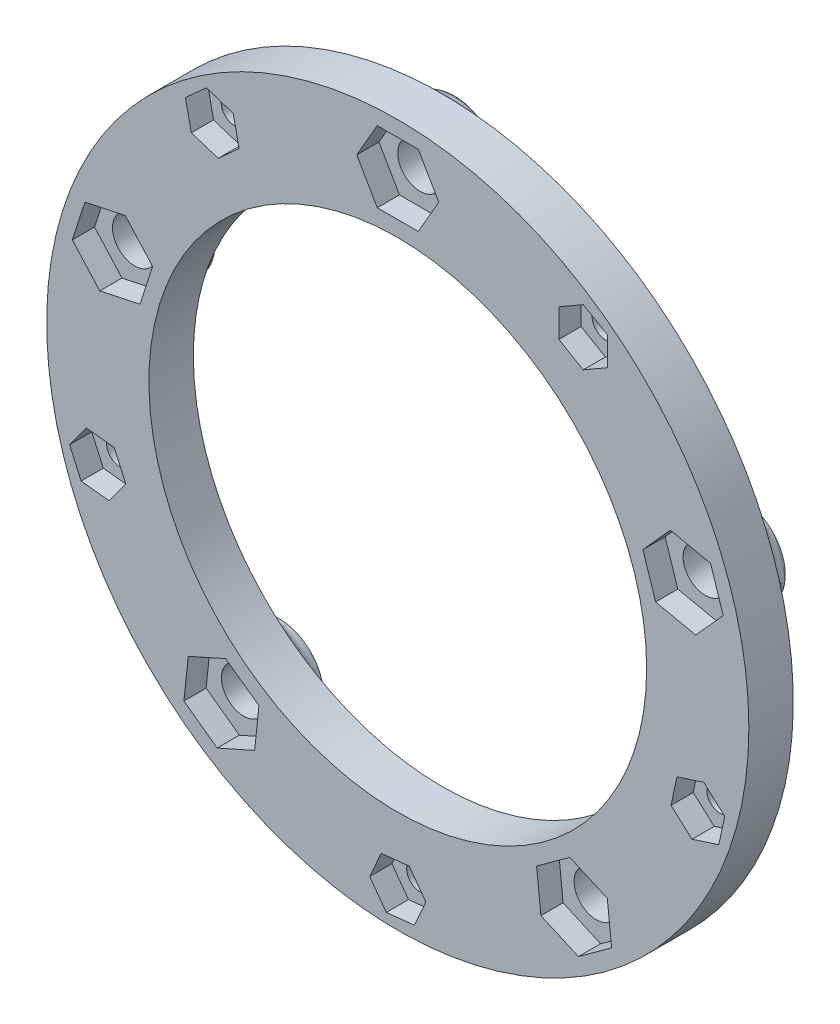
SolidWorks part; units mm, degrees
material "PLA"
ref_plane "Front Plane" through (0, 0, 0) normal (0, 0, 1) x (1, 0, 0)
ref_plane "Top Plane" through (0, 0, 0) normal (0, 1, 0) x (1, 0, 0)
ref_plane "Right Plane" through (0, 0, 0) normal (1, 0, 0) x (0, 0, -1)
sketch "Sketch2" plane through (0, 0, 0) normal (0, 0, 1) x (1, 0, 0)
  line L0 (0, 33.75) -> (0, 0) construction
  line L1 (0, 0) -> (20.8664, 28.7201) construction
  circle A0 centre (0, 0) radius 39.5
  circle A2 centre (0, 0) radius 33.75 construction
  circle A3 centre (0, 33.75) radius 2.5
  circle A4 centre (0, 0) radius 35.5 construction
  circle A5 centre (32.0982, 10.4293) radius 2.5
  circle A8 centre (20.8664, 28.7201) radius 1.5
  circle A9 centre (33.7625, -10.9701) radius 1.5
  circle A11 centre (0, 0) radius 20 construction
  circle A14 centre (0, 33.75) radius 4.25 construction
  circle A15 centre (0, 0) radius 29.5 construction
  circle A16 centre (19.8378, -27.3043) radius 2.5
  circle A19 centre (0, -35.5) radius 1.5
  circle A20 centre (0, 0) radius 38 construction
  circle A23 centre (0, 0) radius 28
  circle A36 centre (-19.8378, -27.3043) radius 2.5
  circle A37 centre (-32.0982, 10.4293) radius 2.5
  circle A38 centre (-33.7625, -10.9701) radius 1.5
  circle A39 centre (-20.8664, 28.7201) radius 1.5
  point P17 (0, 0)
  point P24 (0, 0)
  dimension "D2" = 67.5
  dimension "D4" = 5
  dimension "D7" = 3
  dimension "D3" = 40
  dimension "D10" = 8.5
  dimension "D5" = 4
  dimension "D11" = 36
  dimension "D12" = 1.5
  dimension "D9" = 1.5
  dimension "D6" = 5
  dimension "D8" = 5
extrude "Boss-Extrude1" add sketch "Sketch2" along normal blind 5
sketch "Sketch3" plane through (0, 0, 5) normal (0, 0, 1) x (1, 0, 0)
  line L0 (0, 33.75) -> (0, 0) construction
  line L13 (-4.6188, 33.75) -> (-2.3094, 29.75)
  line L14 (-2.3094, 29.75) -> (2.3094, 29.75)
  line L15 (2.3094, 29.75) -> (4.6188, 33.75)
  line L16 (4.6188, 33.75) -> (2.3094, 37.75)
  line L17 (2.3094, 37.75) -> (-2.3094, 37.75)
  line L18 (-2.3094, 37.75) -> (-4.6188, 33.75)
  line L20 (20.8664, 25.5447) -> (23.6164, 27.1324)
  line L21 (23.6164, 27.1324) -> (23.6164, 30.3078)
  line L22 (23.6164, 30.3078) -> (20.8664, 31.8955)
  line L23 (20.8664, 31.8955) -> (18.1164, 30.3078)
  line L24 (18.1164, 30.3078) -> (18.1164, 27.1324)
  line L25 (18.1164, 27.1324) -> (20.8664, 25.5447)
  circle A0 centre (0, 33.75) radius 4 construction
  circle A1 centre (20.8664, 28.7201) radius 2.75 construction
  dimension "D1" = 8
  dimension "D2" = 5.5
extrude "Cut-Extrude1" cut sketch "Sketch3" against normal blind 2.5
pattern_circular "CirPattern1" count 5 over 360 about axis through (0, 0, 5) along (0, 0, -1) of "Cut-Extrude1" reverse direction yes
sketch "Sketch4" plane through (0, 0, 0) normal (0, 0, -1) x (-1, 0, 0)
  circle A0 centre (0, 33.75) radius 4
  circle A1 centre (0, 33.75) radius 5
  dimension "D1" = 8
extrude "Boss-Extrude2" add sketch "Sketch4" along normal blind 1.5
fillet "Fillet1" radius 1.5 1 edges at (5, 33.75, 0)
fillet "Fillet2" radius 0.5 4 edges at (0, 38.75, -1.5) (0, 28.75, -1.5) (4.9949, 33.5246, -1.5) (-4.9949, 33.5246, -1.5)
chamfer "Chamfer1" distance 0.25 angle 45 1 edges at (-4, 33.75, -1.5)
pattern_circular "CirPattern2" count 5 over 360 about axis through (0, 0, 5) along (0, 0, -1) of "Fillet1", "Boss-Extrude2", "Chamfer1" reverse direction yes
equation "\"module\" = 0.5"
equation "\"pressure_angle\" = 20.0"
equation "\"h_a\" = 0.5"
equation "\"h_f\" = 0.625"
equation "\"clr_tip_root\" = 0.125"
equation "\"bearing_ID\" = 75"
equation "\"bearing_OD\" = 95"
equation "\"bearing_height\" = 10"
equation "\"clearance_planet\" = 1.5"
equation "\"case_dist\" = 6.5"
equation "\"Motor_case_OD_max\" = 131.3"
equation "\"case_mounting_PCD\" = 123.8"
equation "\"bearing mount thickness\" = 8"
equation "\"case_mounting_hole_dia\" = 3"
equation "\"output_mounting_PCD\" = 103"
equation "\"output_mounting_hole_dia\" = 4"
equation "\"clearance_case_mount_holes_shell_thickness\" = 1"
equation "\"motor_case_OD_base\" = 121.8"
equation "\"sec_carrier_thickness\" = 5"
equation "\"sun_coupler_hub_thickness\" = 4"
equation "\"clearance_sun_coupler_sec_carrier\" = 1.5"
equation "\"clearance_motor_and_case\" = 5"
equation "\"motor_OD\" = 106.8"
equation "\"Motor_case_thickness\" = 2.5"
equation "\"Motor_case_ID\" = 116.8"
equation "\"case_mounting_hole_shift\" = 1.0"
equation "\"output_mounting_nut_wrench_size\" = 7"
equation "\"output_mounting_nut_thickness\" = 3.2"
equation "\"case_mounting_hole_allen_socket_dia\" = 5.5"
equation "\"output_mounting_nut_depth\" = 3"
equation "\"case_mounting_bolt_depth\" = 4.5"
equation "\"Ns\" = 80"
equation "\"Np_b\" = 55"
equation "\"ring_radial_thickness\" = 5"
equation "\"ring_to_chamfer_clearance\" = 1.5"
equation "\"Motor_case_OD_base_to_chamfer\" = 5"
equation "\"pattern_offset_from_motor_case_OD_base\" = 3"
equation "\"pattern_bulge_dia\" = 3"
equation "\"pattern_num_bulge\" = 18"
equation "\"pattern_depth\" = 2"
equation "\"motor_height\" = 47.6"
equation "\"case_mounting_wrench_size\" = 5.5"
equation "\"case_mounting_nut_clearance\" = 2"
equation "\"base_plate_thickness\" = 4"
equation "\"case_mounting_nut_thickness\" = 2.4"
equation "\"case_mounting_surface_height\" = 4"
equation "\"motor_mount_hole_PCD\" = 40"
equation "\"motor_mount_hole_dia\" = 5"
equation "\"motor_mount_hole_num\" = 4"
equation "\"central_hole_offset_from_motor_mount_PCD\" = 5"
equation "\"wire_slot_dist_from_center\" = 45.5"
equation "\"wire_slot_length\" = 10"
equation "\"wire_slot_radius\" = 3"
equation "\"driver_upper_holes_dist_from_center\" = 29"
equation "\"driver_lower_holes_dist_from_center\" = 13"
equation "\"driver_side_holes_dist_from_center\" = 22.5"
equation "\"driver_mount_holes_dia\" = 3"
equation "\"driver_mount_inserts_OD\" = 4.8"
equation "\"driver_mount_thickness\" = 1.5"
equation "\"driver_mount_height\" = 6"
equation "\"air_flow_hole_offset\" = 3"
equation "\"num_planet\" = 5"
equation "\"planet_pin_bolt_dia\" = 5"
equation "\"planet_pin_socket_head_dia\" = 8.5"
equation "\"carrier_PCD\" = 67.5"
equation "\"D2@Sketch2\"=\"carrier_PCD\""
equation "\"D4@Sketch2\"=\"planet_pin_bolt_dia\""
equation "\"D6@Sketch2\"=\"num_planet\""
equation "\"D8@Sketch2\"=\"num_planet\""
equation "\"D1@CirPattern1\"=\"num_planet\""
equation "\"planet_shaft_dia\" = 8"
equation "\"planet_shaft_step_offset\" = 1"
equation "\"carrier_trapezoidal_support_sun_offset\" = 5"
equation "\"carrier_trapezoidal_support_hole_PCD_offset_bearing_ID\" = 4"
equation "\"carrier_trapezoidal_support_hole_dia\" = 3"
equation "\"carrier_trapezoidal_support_hole_socket_head_dia\" = 5.5"
equation "\"carrier_bearing_step_width\" = 1.5"
equation "\"standard_clearance_1_5mm\" = 1.5"
equation "\"standard_fillet_1_5mm\" = 1.5"
equation "\"sun_shaft_bearing_OD\" = 16"
equation "\"sun_shaft_bearing_width\" = 5"
equation "\"standard_bearing_insertion_chamfer\" = 0.5"
equation "\"D7@Sketch2\"=\"carrier_trapezoidal_support_hole_dia\""
equation "\"D3@Sketch2\"=\"Ns\"*\"module\""
equation "\"carrier_trapezoidal_support_hole_wrench_size\" = 5.5"
equation "\"planet_pin_bolt_wrench_size\" = 8"
equation "\"D1@Boss-Extrude1\"=\"sec_carrier_thickness\""
equation "\"D1@Cut-Extrude1\"=\"sec_carrier_thickness\"/2"
equation "\"D1@Sketch4\"=\"planet_shaft_dia\""
equation "\"D2@Sketch4\"=\"planet_shaft_step_offset\""
equation "\"D1@Boss-Extrude2\"=\"clearance_planet\""
equation "\"D1@Fillet1\"=\"standard_fillet_1_5mm\""
equation "\"D1@Chamfer1\"=\"standard_bearing_insertion_chamfer\"/2"
equation "\"D1@Fillet2\"=\"standard_fillet_1_5mm\"/3"
equation "\"D1@CirPattern2\"=\"num_planet\""
equation "\"D10@Sketch2\"= \"planet_pin_socket_head_dia\""
equation "\"D1@Sketch3\"=\"planet_pin_bolt_wrench_size\""
equation "\"D11@Sketch2\"=180/\"num_planet\""
equation "\"D2@Sketch3\"=\"carrier_trapezoidal_support_hole_wrench_size\""
equation "\"pressure angle\" = 20.0"
equation "\"h_b\" = 0.625"
equation "\"dp_s\" = 40.0"
equation "\"db_s\" = 37.58770483143634"
equation "\"fw_s_calc\" = 4.872946430626146"
equation "\"alpha_s\" = 0.8539582918412272"
equation "\"beta_s\" = 0.5420834163175456"
equation "\"dp_p_b\" = 27.5"
equation "\"db_p_b\" = 25.84154707161248"
equation "\"fw_p_s\" = 15.81085678360617"
equation "\"alpha_p_b\" = 0.8539582918412449"
equation "\"beta_p_b\" = 1.564810689044783"
equation "\"planet_bearing_OD\" = 12"
equation "\"planet_bearing_width\" = 3.5"
equation "\"planet_bore\" = 10"
equation "\"motor_output_hole_PCD\" = 23"
equation "\"motor_output_hole_dia\" = 4"
equation "\"motor_output_hole_num\" = 4"
equation "\"sun_shaft_bearing_ID\" = 8"
equation "\"sun_hub_dia\" = 30.0"
equation "\"sun_central_bolt_dia\" = 5"
equation "\"sun_central_bolt_socket_head_dia\" = 8.5"
equation "\"fw_s_used\" = 44.67596466627659"
equation "\"motor_output_hole_CSK_OD\" = 8"
equation "\"motor_output_hole_CSK_head_height\" = 2.0"
equation "\"bearing_retainer_thickness\" = 2"
equation "\"Np_s\" = 35"
equation "\"fw_p_b\" = 21.365107882670422"
equation "\"dp_p_s\" = 17.5"
equation "\"db_p_s\" = 16.444620863753396"
equation "\"alpha_p_s\" = 0.8539582918412556"
equation "\"beta_p_s\" = 3.434940559174632"
equation "\"Nr_b\" = 190"
equation "\"dp_r_b\" = 95.0"
equation "\"db_r_b\" = 89.2707989746613"
equation "\"fw_r_b\" = 21.365107882670422"
equation "\"alpha_r_b\" = 0.8539582918412414"
equation "\"beta_r_b\" = 2.655285004735114"
equation "\"ring_OD_b\" = 105.0"
equation "\"Fillet10\"= IIF ( \"ring_OD_b\" > ( \"bearing_OD\" + 2 * \"bearing mount thickness\" ) , \"suppressed\" , \"unsuppressed\" )"
equation "\"Fillet11\"= IIF ( \"ring_OD_b\" < ( \"bearing_OD\" + 2 * \"bearing mount thickness\" ) , \"suppressed\" , \"unsuppressed\" )"
equation "\"Nr_s\" = 170"
equation "\"clr_tip_root_s\" = 0.125"
equation "\"dp_r_s\" = 85.0"
equation "\"db_r_s\" = 79.87387276680222"
equation "\"fw_r_s\" = 14.31085678360617"
equation "\"alpha_r_s\" = 0.8539582918412307"
equation "\"beta_r_s\" = 2.766740113094226"
equation "\"D9@Sketch2\"=\"standard_clearance_1_5mm\""
equation "\"small_ring_case_thickness\" = 4"
equation "\"carrier_thickness\" = 4"
equation "\"small_ring_output_wall_thickness\" = 5"
equation "\"small_ring_output_wall_to_bearing_shaft_attachement_hole_dia\" = 4"
equation "\"small_ring_output_wall_to_bearing_shaft_attachement_hole_depth\" = 6.5"
equation "\"small_ring_output_wall_to_bearing_shaft_attachement_nut_wrench\" = 7"
equation "\"small_ring_output_wall_to_bearing_shaft_attachement_nut_thickness\" = 3.2"
equation "\"small_ring_output_wall_to_bearing_shaft_attachement_hole_pcd\" = 12"
equation "\"small_ring_output_wall_to_bearing_shaft_attachement_hole_num\" = 3"
equation "\"small_ring_output_wall_to_bearing_shaft_attachement_hole_CSK_OD\" = 8"
equation "\"small_ring_output_wall_to_bearing_shaft_attachement_hole_CSK_head_height\" = 2.0"
equation "\"carrier_small_ring_inner_bearing_ID\" = 20"
equation "\"carrier_small_ring_inner_bearing_OD\" = 32"
equation "\"carrier_small_ring_inner_bearing_height\" = 7"
equation "\"carrier_small_ring_inner_bearing_flap\" = 2"
